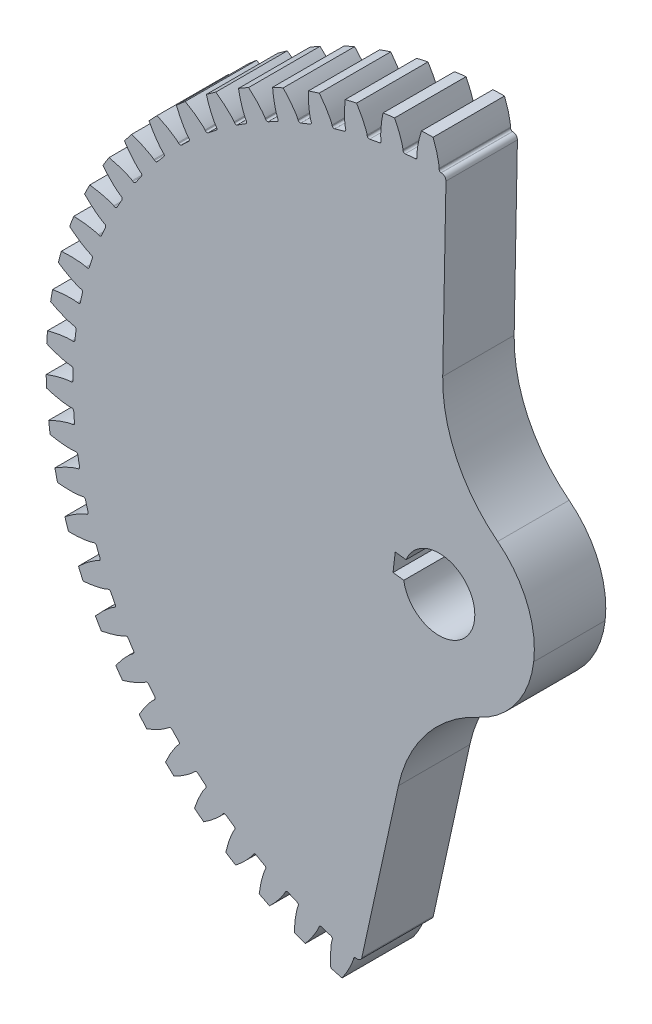
SolidWorks part; units mm, degrees
ref_plane "Front Plane" through (0, 0, 0) normal (0, 0, 1) x (1, 0, 0)
ref_plane "Top Plane" through (0, 0, 0) normal (0, 1, 0) x (1, 0, 0)
ref_plane "Right Plane" through (0, 0, 0) normal (1, 0, 0) x (0, 0, -1)
ref_axis "Centerline" through (0, 0, -5.2388) along (0, 0, 1)
sketch "Sketch1" plane through (0, 0, 0) normal (0, 0, 1) x (1, 0, 0)
  circle A0 centre (0, 0) radius 52.3875
  dimension "D1" = 104.775
extrude "Boss-Extrude1" add sketch "Sketch1" along normal mid plane 9.525
sketch "Sketch2" plane through (0, 0, 0) normal (0, 0, 1) x (1, 0, 0)
  line L0 (49.1819, 0) -> (49.0795, 0)
  line L1 (-48.8068, 0.9274) -> (-52.378, 0.9952) construction
  line L2 (49.1464, -1.8683) -> (49.0441, -1.8645)
  circle A0 centre (0, 0) radius 50.8 construction
  circle A1 centre (0, 0) radius 49.1819 construction
  circle A2 centre (0, 0) radius 48.8156 construction
  arc A3 (48.8149, -0.2632) -> (48.7897, -1.5914) centre (0, 0) cw
  circle A4 centre (0, 0) radius 52.3875 construction
  arc A5 (48.7897, -1.5914) -> (49.0441, -1.8645) centre (49.0541, -1.6001) ccw
  arc A6 (49.0795, 0) -> (48.8149, -0.2632) centre (49.0795, -0.2646) ccw
  arc A7 (58.7102, 4.4762) -> (58.4977, -6.7033) centre (0, 0) cw
  spline S0 degree 4 poles (49.1819, 0) (49.1977, 0.0002) (49.2418, 0.0015) (49.3253, 0.0066) (49.4613, 0.0188) (49.6344, 0.0399) (49.8576, 0.0736) (50.1197, 0.1216) (50.407, 0.1829) (50.7184, 0.2588) (51.0279, 0.3428) (51.3355, 0.4341) (51.6408, 0.5319) (52.0092, 0.6584) (52.4489, 0.8212) (52.9594, 1.0278) (53.5343, 1.281) (54.1152, 1.5593) (54.6827, 1.8497) (55.2508, 2.1619) (55.7968, 2.4774) (56.358, 2.8242) (56.873, 3.154) (57.4432, 3.5444) (57.9013, 3.8656) (58.4977, 4.3112) (58.8476, 4.5811) (59.2542, 4.9043) (59.4333, 5.0518) (59.5437, 5.1426) knots 0 0 0 0 0 0.005377 0.015084 0.028532 0.04661 0.064855 0.092111 0.119476 0.146842 0.174209 0.201575 0.228941 0.256307 0.307035 0.361767 0.4165 0.471232 0.525964 0.580697 0.635429 0.690161 0.744894 0.799626 0.854358 0.909091 0.954545 1 1 1 1 1 construction
  spline S1 degree 4 poles (49.1819, 0) (49.1977, 0.0002) (49.2418, 0.0015) (49.3253, 0.0066) (49.4613, 0.0188) (49.6344, 0.0399) (49.8576, 0.0736) (50.1197, 0.1216) (50.407, 0.1829) (50.7184, 0.2588) (51.0279, 0.3428) (51.3355, 0.4341) (51.6408, 0.5319) (52.0092, 0.6584) (52.4489, 0.8212) (52.9594, 1.0278) (53.5343, 1.281) (54.1152, 1.5593) (54.6827, 1.8497) (55.2508, 2.1619) (55.7968, 2.4774) (56.358, 2.8242) (56.873, 3.154) (57.4432, 3.5444) (57.9013, 3.8656) (58.3684, 4.2146) (58.5948, 4.387) (58.7102, 4.4762) knots 0 0 0 0 0 0.005377 0.015084 0.028532 0.04661 0.064855 0.092111 0.119476 0.146842 0.174209 0.201575 0.228941 0.256307 0.307035 0.361767 0.4165 0.471232 0.525964 0.580697 0.635429 0.690161 0.744894 0.799626 0.854358 0.909091 0.909091 0.909091 0.909091 0.909091
  spline S2 degree 4 poles (49.1464, -1.8683) (49.1621, -1.8692) (49.2062, -1.8721) (49.2894, -1.8804) (49.4249, -1.8978) (49.597, -1.9254) (49.8188, -1.9676) (50.079, -2.0255) (50.3637, -2.0976) (50.6719, -2.1853) (50.978, -2.281) (51.282, -2.3839) (51.5833, -2.4932) (51.9467, -2.6337) (52.3798, -2.8131) (52.8822, -3.0389) (53.447, -3.3138) (54.0169, -3.6139) (54.573, -3.9257) (55.1288, -4.2593) (55.6624, -4.5952) (56.21, -4.9631) (56.7122, -5.3122) (57.2671, -5.724) (57.7126, -6.0624) (58.2917, -6.5304) (58.6311, -6.8133) (59.0252, -7.1518) (59.1985, -7.306) (59.3053, -7.4008) knots 0 0 0 0 0 0.005377 0.015084 0.028532 0.04661 0.064855 0.092111 0.119476 0.146842 0.174209 0.201575 0.228941 0.256307 0.307035 0.361767 0.4165 0.471232 0.525964 0.580697 0.635429 0.690161 0.744894 0.799626 0.854358 0.909091 0.954545 1 1 1 1 1 construction
  spline S3 degree 4 poles (49.1464, -1.8683) (49.1621, -1.8692) (49.2062, -1.8721) (49.2894, -1.8804) (49.4249, -1.8978) (49.597, -1.9254) (49.8188, -1.9676) (50.079, -2.0255) (50.3637, -2.0976) (50.6719, -2.1853) (50.978, -2.281) (51.282, -2.3839) (51.5833, -2.4932) (51.9467, -2.6337) (52.3798, -2.8131) (52.8822, -3.0389) (53.447, -3.3138) (54.0169, -3.6139) (54.573, -3.9257) (55.1288, -4.2593) (55.6624, -4.5952) (56.21, -4.9631) (56.7122, -5.3122) (57.2671, -5.724) (57.7126, -6.0624) (58.1662, -6.4289) (58.3859, -6.6098) (58.4977, -6.7033) knots 0 0 0 0 0 0.005377 0.015084 0.028532 0.04661 0.064855 0.092111 0.119476 0.146842 0.174209 0.201575 0.228941 0.256307 0.307035 0.361767 0.4165 0.471232 0.525964 0.580697 0.635429 0.690161 0.744894 0.799626 0.854358 0.909091 0.909091 0.909091 0.909091 0.909091
  point P22 (48.1402, -8.0923)
  point P25 (48.8156, 0)
  dimension "D1" = 101.6
  dimension "D2" = 98.3638
  dimension "D3" = 97.6313
  dimension "D6" = 0.2646
  dimension "D4" = 1.089
  dimension "D5" = 1.089
extrude "Cut-Extrude1" cut sketch "Sketch2" against normal through all both and the other way through all
pattern_circular "CirPattern1" count 64 over 360 about axis through (0, 0, -5.2388) along (0, 0, 1) of "Cut-Extrude1"
sketch "Sketch3" plane through (0, 0, 4.7625) normal (0, 0, 1) x (1, 0, 0)
  circle A0 centre (0, 0) radius 4.7625
  dimension "D1" = 9.525
extrude "Cut-Extrude2" cut sketch "Sketch3" against normal through all
sketch "Sketch4" plane through (0, 0, 4.7625) normal (0, 0, 1) x (1, 0, 0)
  line L0 (0.9274, 48.8068) -> (0.2424, 12.7591)
  line L1 (-2.727, -12.4667) -> (-10.4313, -47.6881)
  line L2 (0.9274, 48.8068) -> (1.0857, 57.1397)
  line L3 (-10.4313, -47.6881) -> (-12.2123, -55.8299)
  line L4 (0, 0) -> (-34.4616, 4.0566) construction
  line L9 (0.2424, 12.7591) -> (14.0976, 11.1282)
  line L10 (14.0976, 11.1282) -> (11.1282, -14.0976)
  line L11 (11.1282, -14.0976) -> (-2.727, -12.4667)
  line L12 (0, 0) -> (12.6129, -1.4847) construction
  line L13 (0.2424, 12.7591) -> (0, 0) construction
  line L14 (0, 0) -> (-2.727, -12.4667) construction
  arc A0 (1.5914, 48.7897) -> (0.2632, 48.8149) centre (0, 0) ccw construction
  arc A3 (-11.0793, -47.5417) -> (-9.7814, -47.8256) centre (0, 0) ccw construction
  arc A4 (-12.2123, -55.8299) -> (1.0857, 57.1397) centre (0, 0) ccw
  dimension "D1" = 57.15
  dimension "D2" = 168.75
  dimension "D3" = 84.375
  dimension "D4" = 12.7
  dimension "D5" = 25.4
extrude "Cut-Extrude3" cut sketch "Sketch4" against normal through all
fillet "Fillet1" radius 12.7 2 edges at (11.1282, -14.0976, 0) (14.0976, 11.1282, 0)
fillet "Fillet2" radius 19.05 2 edges at (-2.727, -12.4667, 0) (0.2424, 12.7591, 0)
sketch "Sketch5" plane through (0, 0, 4.7625) normal (0, 0, 1) x (1, 0, 0)
  line L0 (12.6129, -1.4847) -> (0, 0) construction
  line L1 (0, 0) -> (-16.4549, 1.937) construction
  line L2 (-5.848, 1.9671) -> (-4.4101, 1.7979)
  line L3 (-5.848, 1.9671) -> (-6.1449, -0.5554)
  line L4 (-4.4101, 1.7979) -> (-4.707, -0.7247)
  line L5 (-6.1449, -0.5554) -> (-4.707, -0.7247)
  circle A0 centre (0, 0) radius 4.7625 construction
  point P4 (0, 0)
  point P12 (0, 0)
  dimension "D1" = 1.4478
  dimension "D2" = 2.54
extrude "Cut-Extrude4" cut sketch "Sketch5" against normal through all
fillet "Fillet3" radius 0.635 2 edges at (0.9274, 48.8068, 0) (-10.4313, -47.6881, 0)
equation "\"p\"= 16'Diametral pitch"
equation "\"N\" = 64'Numer of teeth"
equation "\"Phi\"= 14.5'Pressure angle"
equation "\"a\"= 1 / \"p\"'Addendum"
equation "\"b\"= 1.25 / \"p\"'Dedendum"
equation "\"dp\"= \"N\" / \"p\"'Pitch circle diameter"
equation "\"db\"= \"dp\" * cos ( \"Phi\" )'base circle diameter"
equation "\"c\"= \"b\" - \"a\"'Clearance"
equation "\"alpha\"= sqr ( \"dp\" ^ 2 - \"db\" ^ 2 ) / \"db\" * 180 / pi - \"Phi\""
equation "\"W\"= .375'Face width"
equation "\"D1@Sketch1\"= \"dp\" + 2 * \"a\""
equation "\"D1@Boss-Extrude1\"=\"W\""
equation "\"D1@Sketch2\"=\"dp\""
equation "\"D2@Sketch2\"= \"db\""
equation "\"D3@Sketch2\"=\"dp\" - 2*\"b\""
equation "\"D4@Sketch2\" = 360 / ( 4 * \"N\" ) - \"alpha\""
equation "\"D5@Sketch2\"=\"D4@Sketch2\""
equation "\"D6@Sketch2\"= \"c\" * 2 / 3"
equation "\"D1@CirPattern1\"=\"N\""
equation "\"D3@Sketch4\"=\"D2@Sketch4\"/2"
equation "\"c\"= 1"
